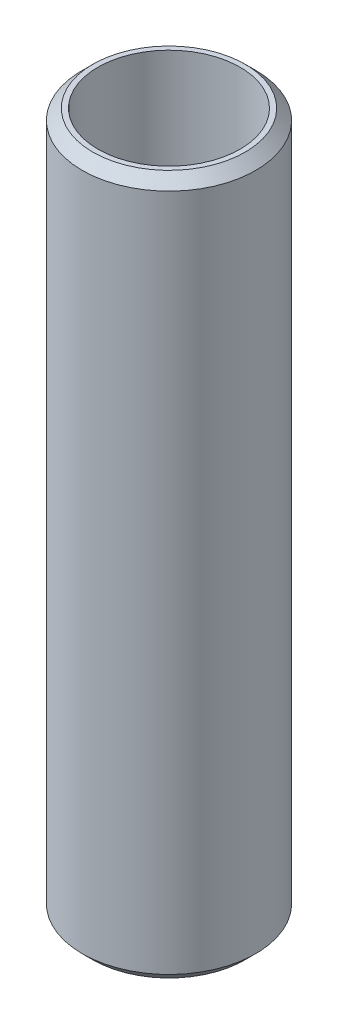
SolidWorks part; units mm, degrees
ref_plane "Front Plane" through (0, 0, 0) normal (0, 0, 1) x (1, 0, 0)
ref_plane "Top Plane" through (0, 0, 0) normal (0, 1, 0) x (1, 0, 0)
ref_plane "Right Plane" through (0, 0, 0) normal (1, 0, 0) x (0, 0, -1)
sketch "Sketch1" plane through (0, 0, 0) normal (0, 1, 0) x (1, 0, 0)
  circle A0 centre (0, 0) radius 47.5
  dimension "SHAFT_OD" = 95
extrude "Boss-Extrude1" add sketch "Sketch1" along normal blind 383.1077
sketch "Sketch2" plane through (0, 0, 0) normal (0, 1, 0) x (1, 0, 0)
  circle A0 centre (0, 0) radius 38.9338
  dimension "BORE_D" = 77.8676
extrude "Cut-Extrude1" cut sketch "Sketch2" along normal through all
chamfer "Chamfer1" distance 5.7776 angle 45 2 edges at (0, 383.1077, 47.5) (0, 0, 47.5)
